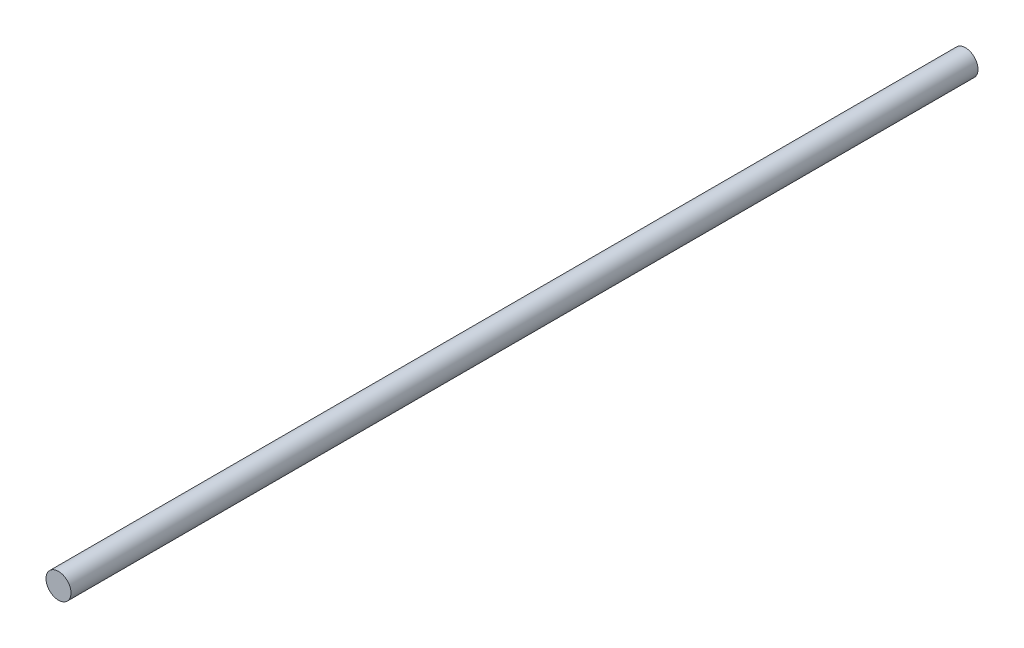
SolidWorks part; units mm, degrees
material "AISI 316 Stainless Steel Sheet (SS)"
ref_plane "Front (1)" through (0, 0, 0) normal (0, 0, 1) x (1, 0, 0)
ref_plane "Top (2)" through (0, 0, 0) normal (0, 1, 0) x (1, 0, 0)
ref_plane "Right (3)" through (0, 0, 0) normal (1, 0, 0) x (0, 0, -1)
ref_axis "X Axis" through (13.5064, 0, 0) along (-1, 0, 0)
ref_axis "Y Axis" through (0, 12.3593, 0) along (0, -1, 0)
ref_axis "Z Axis" through (0, 0, 14.1119) along (0, 0, -1)
sketch "Sketch2" plane through (0, 0, 0) normal (1, 0, 0) x (0, 0, -1)
  line L1 (0, 0) -> (290, 0)
  line L2 (0, 0) -> (0, 4)
  line L3 (0, 4) -> (290, 4)
  line L4 (290, 0) -> (290, 4)
  dimension "D1" = 290
  dimension "D2" = 4
revolve "Revolve1" add sketch "Sketch2" angle 360 about L1
cosmetic thread "Cosmetic Thread2" parameters "D2"=6.891
